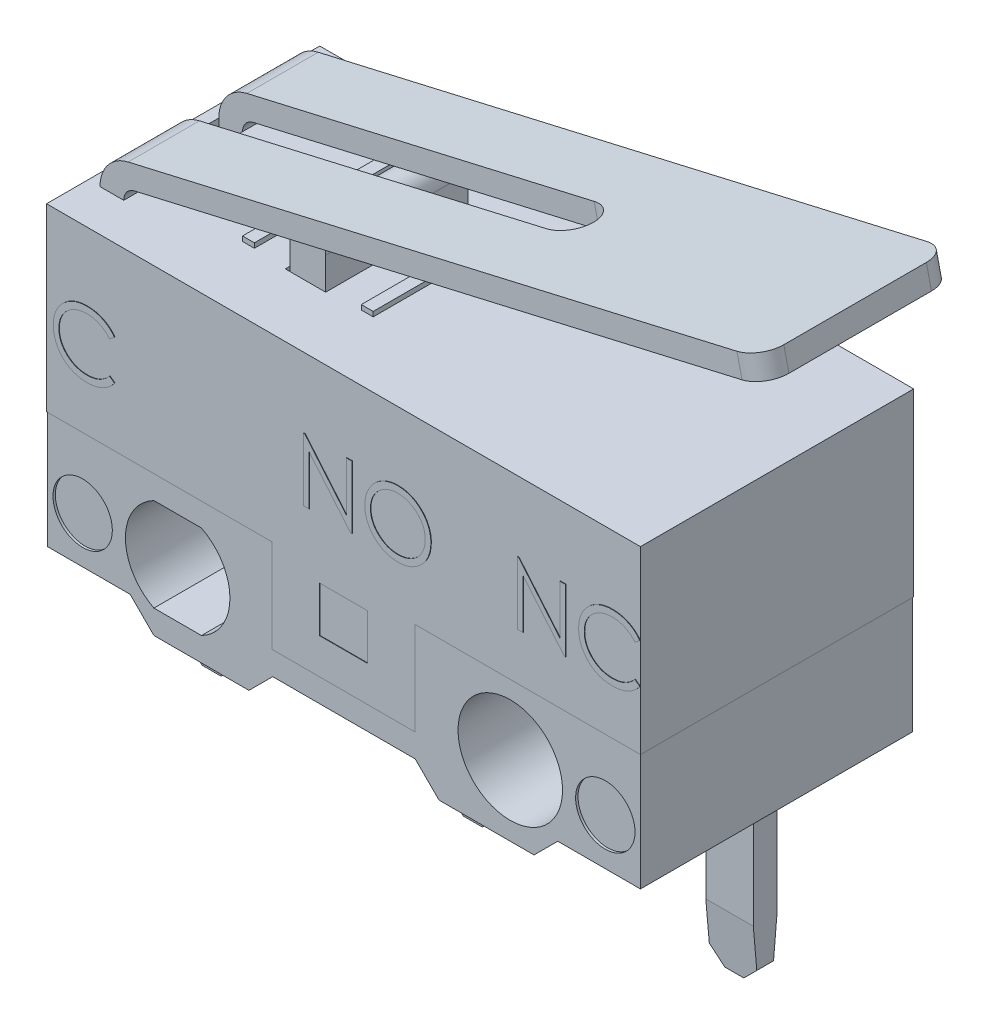
SolidWorks part; units mm, degrees
ref_plane "Plan de face" through (0, 0, 0) normal (0, 0, 1) x (1, 0, 0)
ref_plane "Plan de dessus" through (0, 0, 0) normal (0, 1, 0) x (1, 0, 0)
ref_plane "Plan de droite" through (0, 0, 0) normal (1, 0, 0) x (0, 0, -1)
sketch "Esquisse1" plane through (0, 0, 0) normal (0, 0, 1) x (1, 0, 0)
  line L1 (-6.5, 3.375) -> (6.5, 3.375)
  line L2 (-6.5, 3.375) -> (-6.5, -3.375)
  line L3 (-6.5, -3.375) -> (6.5, -3.375)
  line L4 (6.5, 3.375) -> (6.5, -3.375)
  line L5 (-6.5, 3.375) -> (6.5, -3.375) construction
  line L6 (-6.5, -3.375) -> (6.5, 3.375) construction
  point P0 (0, 0)
  dimension "D1" = 6.75
  dimension "D2" = 13
extrude "Boss.-Extru.1" add sketch "Esquisse1" along normal blind 5.75
ref_plane "Plan1" through (0, 0, 2.875) normal (0, 0, 1) x (1, 0, 0)
sketch "Esquisse6" plane through (0, 0, 5.75) normal (0, 0, 1) x (1, 0, 0)
  line L0 (-6.5, -2.875) -> (-4.5, -2.875)
  line L1 (-6.5, 3.375) -> (-6.5, -3.375) construction
  line L2 (-4.5, -2.875) -> (-4, -3.375)
  line L3 (-6.5, -3.375) -> (6.5, -3.375) construction
  line L4 (-4, -3.375) -> (-2, -3.375)
  line L5 (-2, -3.375) -> (-1.5, -2.875)
  line L6 (-1.5, -2.875) -> (1.5, -2.875)
  line L7 (1.5, -2.875) -> (2, -3.375)
  line L8 (2, -3.375) -> (4, -3.375)
  line L9 (4, -3.375) -> (4.5, -2.875)
  line L10 (4.5, -2.875) -> (6.5, -2.875)
  line L11 (6.5, -3.375) -> (6.5, 3.375) construction
  line L12 (6.5, -2.875) -> (6.5, -4.2145)
  line L13 (6.5, -4.2145) -> (-6.5, -4.2145)
  line L14 (-6.5, -4.2145) -> (-6.5, -2.875)
  dimension "D1" = 0.5
  dimension "D2" = 135
  dimension "D3" = 135
  dimension "D4" = 135
  dimension "D5" = 2
  dimension "D6" = 2
  dimension "D7" = 2
  dimension "D8" = 2
extrude "Enlèv. mat.-Extru.1" cut sketch "Esquisse6" against normal up to surface (5.75 mm away) up to face at (0, 0, 0)
sketch "Esquisse4" plane through (0, 0, 2.875) normal (0, 0, 1) x (1, 0, 0)
  line L0 (-6, -2.875) -> (-6, -6.125)
  line L9 (-5, -6.125) -> (-5, -2.875)
  line L10 (-5, -2.875) -> (-6, -2.875)
  line L11 (-5.5, -2.875) -> (-5.5, -7.9439) construction
  line L15 (-6, -6.125) -> (-5, -6.125)
  line L16 (-4.5, -2.875) -> (-6.5, -2.875) construction
  line L17 (-6.5, 3.375) -> (-6.5, -2.875) construction
  dimension "D1" = 1
  dimension "D2" = 1
  dimension "D4" = 3.25
extrude "Boss.-Extru.2" add sketch "Esquisse4" along normal blind 0.25 and the other way blind 0.25
chamfer "Chanfrein1" distance 0.3 angle 45 2 edges at (-5, -6.125, 2.875) (-6, -6.125, 2.875)
chamfer "Chanfrein2" distance 0.1 angle 85 2 edges at (-5.5, -6.125, 2.625) (-5.5, -6.125, 3.125)
pattern_linear "Répétition linéaire1" count 3 spacing 5.5 along (1, 0, 0) of "Boss.-Extru.2", "Chanfrein1", "Chanfrein2"
sketch "Esquisse7" plane through (0, 0, 5.75) normal (0, 0, 1) x (1, 0, 0)
  line L0 (-4, -2.875) -> (-3, -2.875)
  line L1 (-4, -0.9154) -> (-3, -0.9154)
  line L2 (-3.5, -1.8952) -> (3.5, -1.8952) construction
  line L3 (-4, -3.375) -> (-2, -3.375) construction
  line L4 (-6.5, 3.375) -> (-6.5, -2.875) construction
  line L5 (6.5, -2.875) -> (6.5, 3.375) construction
  arc A0 (-4, -0.9154) -> (-4, -2.875) centre (-3.5, -1.8952) ccw
  arc A1 (-3, -0.9154) -> (-3, -2.875) centre (-3.5, -1.8952) cw
  circle A2 centre (3.5, -1.8952) radius 1.1
  dimension "D1" = 1.1
  dimension "D3" = 1.1
  dimension "D4" = 2.2
  dimension "D2" = 1
  dimension "D5" = 0.5
  dimension "D6" = 3
  dimension "D7" = 3
extrude "Enlèv. mat.-Extru.2" cut sketch "Esquisse7" against normal up to surface (5.75 mm away) up to face at (0, -2, 0)
sketch "Esquisse8" plane through (0, 0, 5.75) normal (0, 0, 1) x (1, 0, 0)
  line L0 (-6.5, -0.4154) -> (-1.5, -0.4154)
  line L1 (-6.5, 3.375) -> (-6.5, -2.875) construction
  line L2 (-1.5, -0.4154) -> (-1.5, -2.375)
  line L3 (-1.5, -2.375) -> (1.5, -2.375)
  line L4 (1.5, -2.375) -> (1.5, -0.4154)
  line L5 (1.5, -0.4154) -> (6.5, -0.4154)
  line L6 (6.5, -2.875) -> (6.5, 3.375) construction
  line L7 (6.5, -0.4154) -> (6.5, -4.9919)
  line L8 (6.5, -4.9919) -> (-6.5, -4.9919)
  line L9 (-6.5, -4.9919) -> (-6.5, -0.4154)
  line L10 (1.5, -2.875) -> (-1.5, -2.875) construction
  line L11 (-3, -0.9154) -> (-4, -0.9154) construction
  line L13 (-0.5, -0.6654) -> (0.5, -0.6654)
  line L14 (-0.5, -0.6654) -> (-0.5, -1.625)
  line L15 (-0.5, -1.625) -> (0.5, -1.625)
  line L16 (0.5, -0.6654) -> (0.5, -1.625)
  line L17 (-0.5, -0.6654) -> (0.5, -1.625) construction
  line L18 (-0.5, -1.625) -> (0.5, -0.6654) construction
  point P21 (0, -1.1452)
  dimension "D1" = 0.5
  dimension "D2" = 0.5
  dimension "D3" = 0.25
  dimension "D4" = 1
  dimension "D5" = 1
  dimension "D6" = 0.75
extrude "Enlèv. mat.-Extru.3" cut sketch "Esquisse8" against normal blind 0.01
sketch "Esquisse9" plane through (0, 0, 5.74) normal (0, 0, 1) x (1, 0, 0)
  line L0 (-5.5, -1.8952) -> (5.5, -1.8952) construction
  line L1 (6.5, -2.875) -> (6.5, -0.4154) construction
  line L2 (-6.5, -0.4154) -> (-6.5, -2.875) construction
  circle A0 centre (-5.5, -1.8952) radius 0.625
  circle A1 centre (5.5, -1.8952) radius 0.625
  point P4 (3.5, -1.8952)
  dimension "D1" = 1.25
  dimension "D2" = 1.25
  dimension "D3" = 1
  dimension "D4" = 1
extrude "Enlèv. mat.-Extru.4" cut sketch "Esquisse9" against normal blind 0.05
mirror "Symétrie1" about plane through (0, 0, 2.875) normal (0, 0, 1) of "Enlèv. mat.-Extru.4", "Enlèv. mat.-Extru.3"
sketch "Esquisse10" plane through (-6.5, 0, 0) normal (-1, 0, 0) x (0, 0, 1)
  line L1 (0.01, -2.875) -> (5.74, -2.875)
  line L2 (0.01, -2.875) -> (0.01, -0.4154)
  line L3 (0.01, -0.4154) -> (5.74, -0.4154)
  line L4 (5.74, -2.875) -> (5.74, -0.4154)
extrude "Enlèv. mat.-Extru.5" cut sketch "Esquisse10" against normal blind 0.01
sketch "Esquisse11" plane through (6.5, 0, 0) normal (1, 0, 0) x (0, 0, -1)
  line L1 (-5.74, -2.875) -> (-0.01, -2.875)
  line L2 (-5.74, -2.875) -> (-5.74, -0.4154)
  line L3 (-5.74, -0.4154) -> (-0.01, -0.4154)
  line L4 (-0.01, -2.875) -> (-0.01, -0.4154)
extrude "Enlèv. mat.-Extru.6" cut sketch "Esquisse11" against normal blind 0.01
sketch "Esquisse12" plane through (0, 0, 5.75) normal (0, 0, 1) x (1, 0, 0)
  line L0 (-6.2, 0.5846) -> (-4.55, 0.5846) construction
  line L4 (-1, 0.5846) -> (2.5, 0.5846) construction
  line L5 (3.5, 0.5846) -> (6.2, 0.5846) construction
  line L6 (-1.5, -0.4154) -> (-6.5, -0.4154) construction
  line L7 (-6.5, 3.375) -> (-6.5, -0.4154) construction
  line L8 (6.5, -0.4154) -> (6.5, 3.375) construction
  text T0 "C" font "Century Gothic" height in points 5
  text T1 "NO" font "Century Gothic" height in points 5
  text T2 "NC" font "Century Gothic" height in points 5
  dimension "D1" = 1
  dimension "D2" = 1.65
  dimension "D3" = 0.3
  dimension "D4" = 0.3
  dimension "D5" = 2.7
  dimension "D6" = 3.5
  dimension "D7" = 1
extrude "Boss.-Extru.3" add sketch "Esquisse12" along normal blind 0.01
sketch "Esquisse13" plane through (0, 0, 2.875) normal (0, 0, 1) x (1, 0, 0)
  line L0 (-1.75, 4) -> (-1.75, 3.375)
  line L1 (6.5, 3.375) -> (-6.5, 3.375) construction
  line L2 (-1.75, 3.375) -> (-2.5, 3.375)
  line L3 (-2.5, 3.375) -> (-2.5, 4)
  line L4 (-4.7467, 4.375) -> (-2.1308, 4.375) construction
  line L5 (-6.5, 3.375) -> (-6.5, -0.4154) construction
  line L6 (-3.5, 3.375) -> (-3.5, 3.475)
  line L7 (-3.5, 3.475) -> (-3.25, 3.475)
  line L8 (-3.25, 3.475) -> (-3.25, 3.375)
  line L9 (-3.25, 3.375) -> (-3.5, 3.375)
  line L10 (-1, 3.375) -> (-1, 3.475)
  line L11 (-1, 3.475) -> (-0.75, 3.475)
  line L12 (-0.75, 3.475) -> (-0.75, 3.375)
  line L13 (-0.75, 3.375) -> (-1, 3.375)
  arc A0 (-2.5, 4) -> (-1.75, 4) centre (-2.125, 4) cw
  dimension "D1" = 0.75
  dimension "D2" = 1
  dimension "D3" = 4
  dimension "D4" = 0.1
  dimension "D5" = 0.75
  dimension "D6" = 0.75
  dimension "D7" = 0.25
  dimension "D8" = 0.25
extrude "Boss.-Extru.4" add sketch "Esquisse13" along normal blind 1.5 and the other way blind 1.5
sketch "Esquisse14" plane through (0, 3.375, 0) normal (0, 1, 0) x (1, 0, 0)
  line L1 (-2.5, -1.375) -> (-1.75, -1.375)
  line L2 (-2.5, -1.375) -> (-2.5, -4.375)
  line L3 (-2.5, -4.375) -> (-1.75, -4.375)
  line L4 (-1.75, -1.375) -> (-1.75, -4.375)
  line L8 (-6.5, -5.75) -> (-6.5, 0) construction
  line L9 (-6, -0.875) -> (-5.5, -0.875)
  line L10 (-6, -0.875) -> (-6, -4.875)
  line L11 (-6, -4.875) -> (-5.5, -4.875)
  line L12 (-2.55, -1.325) -> (-2.55, -4.425)
  line L13 (-2.55, -4.425) -> (-1.7, -4.425)
  line L14 (-1.7, -4.425) -> (-1.7, -1.325)
  line L15 (-1.7, -1.325) -> (-2.55, -1.325)
  line L16 (-2.55, -1.325) -> (-2.55, -4.425)
  line L17 (-2.55, -4.425) -> (-1.7, -4.425)
  line L18 (-1.7, -4.425) -> (-1.7, -1.325)
  line L19 (-1.7, -1.325) -> (-2.55, -1.325)
  line L20 (-5.5, -0.875) -> (-5.5, -4.875)
  line L21 (-6, -2.875) -> (-3.9155, -2.875) construction
  line L22 (-3.7125, -2.875) -> (3.7125, -2.875) construction
  dimension "D2" = 0.5
  dimension "D3" = 0.5
  dimension "D4" = 4
  dimension "D1" = 0.05
extrude "Enlèv. mat.-Extru.7" cut sketch "Esquisse14" against normal blind 2
sketch "Esquisse16" plane through (0, 0, 0.875) normal (0, 0, 1) x (1, 0, 0)
  line L0 (-6, 2.375) -> (-5.5, 2.375)
  line L1 (-5.5, 2.375) -> (-5.5, 3.375)
  line L2 (-5.2748, 3.6581) -> (8, 6.7211)
  line L3 (8, 6.7211) -> (7.8921, 7.1888)
  line L4 (7.8921, 7.1888) -> (-5.4072, 4.1201)
  line L5 (-6, 3.375) -> (-6, 2.375)
  line L6 (-6.5, 3.375) -> (-6.5, -0.4154) construction
  line L7 (6.5, 3.375) -> (-6.5, 3.375) construction
  line L8 (8, 6.7211) -> (8, 3.9001) construction
  line L9 (6.5, -0.4154) -> (6.5, 3.375) construction
  line L10 (6.5, 2.5145) -> (6.5, 9.8405) construction
  arc A0 (-5.5, 3.375) -> (-5.2748, 3.6581) centre (-5.2095, 3.375) cw
  arc A2 (-1.75, 4) -> (-2.5, 4) centre (-2.125, 4) ccw construction
  arc A3 (-6, 3.375) -> (-5.4072, 4.1201) centre (-5.2353, 3.375) cw
  point P8 (6.5, 6.375)
  dimension "D1" = 0.5
  dimension "D2" = 0.5
  dimension "D3" = 0.48
  dimension "D4" = 1
  dimension "D5" = 1.5
  dimension "D6" = 3
extrude "Boss.-Extru.13" add sketch "Esquisse16" along normal blind 4 separate body contours A3 L4 L3 L2 A0 L1 L0 L5
sketch "Esquisse17" plane through (0, 0, 2.875) normal (0, 0, 1) x (1, 0, 0)
  line L6 (-5.4072, 4.1201) -> (2.3879, 5.9188)
  line L7 (7.8921, 7.1888) -> (-5.4072, 4.1201) construction
  line L8 (2.3879, 5.9188) -> (2.4959, 5.4511)
  line L9 (-5.2748, 3.6581) -> (8, 6.7211) construction
  line L10 (2.4959, 5.4511) -> (-5.2748, 3.6581)
  line L12 (-6, 3.375) -> (-6, 2.375)
  line L13 (-6, 2.375) -> (-5.5, 2.375)
  line L14 (-5.5, 2.375) -> (-5.5, 3.375)
  line L15 (-5.2748, 3.6581) -> (8, 6.7211)
  line L16 (8, 6.7211) -> (7.8921, 7.1888)
  line L17 (7.8921, 7.1888) -> (-5.4072, 4.1201)
  line L18 (-6, 3.375) -> (-6, 2.375)
  line L19 (-6, 2.375) -> (-5.5, 2.375)
  line L20 (-5.5, 2.375) -> (-5.5, 3.375)
  arc A4 (-5.4072, 4.1201) -> (-6, 3.375) centre (-5.2353, 3.375) ccw
  arc A5 (-5.2748, 3.6581) -> (-5.5, 3.375) centre (-5.2095, 3.375) ccw
  arc A6 (-5.4072, 4.1201) -> (-6, 3.375) centre (-5.2353, 3.375) ccw
  arc A7 (-5.2748, 3.6581) -> (-5.5, 3.375) centre (-5.2095, 3.375) ccw
  dimension "D2" = 8
  dimension "D1" = 0
extrude "Enlèv. mat.-Extru.8" cut sketch "Esquisse17" against normal blind 0.5 and the other way blind 0.5
fillet "Congé1" radius 0.5 2 edges at (2.4419, 5.6849, 3.375) (2.4419, 5.6849, 2.375)
fillet "Congé3" radius 0.5 2 edges at (7.946, 6.955, 0.875) (7.946, 6.955, 4.875)
sketch "Esquisse19" plane through (0, 0, 0) normal (0, 0, -1) x (-1, 0, 0)
  line L0 (-4.5, -0.1654) -> (5.7239, -0.1654) construction
  line L1 (-6.5, -0.4154) -> (-1.5, -0.4154) construction
  line L2 (-6.5, -0.4154) -> (-6.5, 3.375) construction
  text T0 "2A125VAC" font "Century Gothic" height in points 4
  dimension "D1" = 0.25
  dimension "D2" = 2
extrude "Boss.-Extru.14" add sketch "Esquisse19" along normal blind 0.05
other "Move Face1" face at (-6.49, -1.6452, 2.875) face at (-6.5, 1.4798, 2.875) parameters "D1"=0.25
other "Move Face2" face at (6.49, -1.6452, 2.875) face at (6.5, 1.4798, 2.875) parameters "D1"=0.25
sketch "Sketch1" plane through (0, 0, 5.75) normal (0, 0, 1) x (1, 0, 0)
  line L0 (-6.25, 3.375) -> (-6.25, 3.9257)
  line L1 (-6.25, 3.375) -> (6.24, 3.375)
  line L2 (-6.25, 3.375) -> (-6.25, -2.875)
  line L3 (-6.25, -2.875) -> (6.24, -2.875)
  line L4 (6.24, 3.375) -> (6.24, -2.875)
  line L5 (7.8921, 7.1888) -> (-6.25, 3.9257)
  circle A0 centre (-3.5, -1.8952) radius 1.1
  circle A1 centre (3.5, -1.8952) radius 1.1
